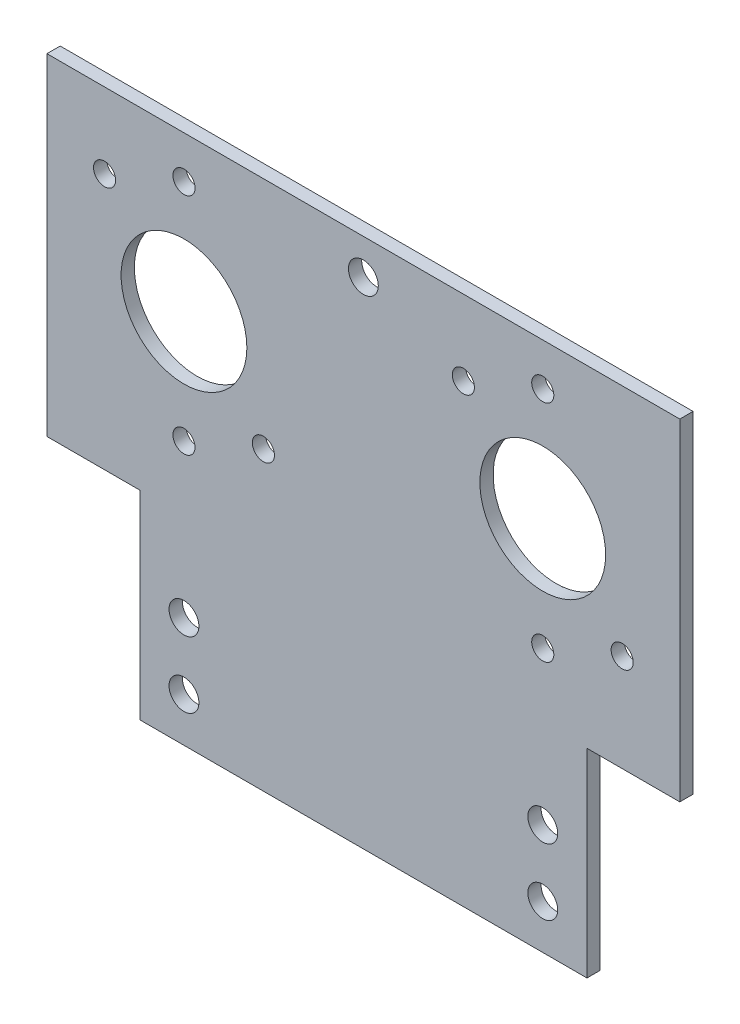
SolidWorks part; units mm, degrees
ref_plane "Front Plane" through (0, 0, 0) normal (0, 0, 1) x (1, 0, 0)
ref_plane "Top Plane" through (0, 0, 0) normal (0, 1, 0) x (1, 0, 0)
ref_plane "Right Plane" through (0, 0, 0) normal (1, 0, 0) x (0, 0, -1)
sketch "Sketch1" plane through (0, 0, 0) normal (0, 0, 1) x (1, 0, 0)
  line L1 (0, 0) -> (143.16, 0)
  line L2 (0, 0) -> (0, -120)
  line L3 (0, -120) -> (143.16, -120)
  line L4 (143.16, 0) -> (143.16, -120)
  dimension "D1" = 120
  dimension "D2" = 143.16
extrude "Boss-Extrude1" add sketch "Sketch1" along normal blind 3
sketch "Sketch2" plane through (0, 0, 3) normal (0, 0, 1) x (1, 0, 0)
  line L0 (0, 0) -> (0, -120) construction
  line L1 (143.16, -120) -> (143.16, 0) construction
  line L2 (0, -120) -> (143.16, -120) construction
  line L3 (143.16, 0) -> (0, 0) construction
  circle A0 centre (31, -35) radius 14.225
  circle A1 centre (112.16, -35) radius 14.225
  circle A2 centre (31, -110) radius 3.375
  circle A5 centre (112.16, -110) radius 3.375
  circle A7 centre (71.58, -8) radius 3.375
  circle A8 centre (31, -95) radius 3.375
  circle A9 centre (112.16, -95) radius 3.375
  point P6 (0, 0)
  point P7 (0, 0)
  point P8 (67.2787, -8)
  point P9 (71.58, 0)
  dimension "D1" = 28.45
  dimension "D2" = 28.45
  dimension "D3" = 6.75
  dimension "D4" = 35
  dimension "D5" = 6.75
  dimension "D7" = 15
  dimension "D8" = 6.75
  dimension "D9" = 31
  dimension "D10" = 31
  dimension "D13" = 15
  dimension "D14" = 10
  dimension "D16" = 8
extrude "Cut-Extrude1" cut sketch "Sketch2" against normal through all
sketch "Sketch3" plane through (0, 0, 0) normal (0, 0, -1) x (-1, 0, 0)
  circle A0 centre (-48.9605, -52.9605) radius 2.0193 construction
  circle A1 centre (-31, -9.6) radius 2.0193 construction
  circle A2 centre (-13.0395, -17.0395) radius 2.0193 construction
  circle A3 centre (-48.9605, -52.9605) radius 2.0193
  circle A4 centre (-31, -9.6) radius 2.0193
  circle A5 centre (-13.0395, -17.0395) radius 2.0193
  circle A6 centre (-31, -60.4) radius 2.0193 construction
  circle A7 centre (-31, -60.4) radius 2.0193
  circle A8 centre (-94.1995, -17.0395) radius 2.0193 construction
  circle A9 centre (-112.16, -9.6) radius 2.0193 construction
  circle A10 centre (-94.1995, -17.0395) radius 2.0193
  circle A11 centre (-112.16, -9.6) radius 2.0193
  circle A12 centre (-112.16, -60.4) radius 2.0193 construction
  circle A13 centre (-130.1205, -52.9605) radius 2.0193 construction
  circle A14 centre (-112.16, -60.4) radius 2.0193
  circle A15 centre (-130.1205, -52.9605) radius 2.0193
  point P25 (-31, -60.4)
  point P26 (-48.9605, -52.9605)
  point P27 (-31, -9.6)
  point P28 (-13.0395, -17.0395)
  point P29 (-112.16, -60.4)
  point P30 (-130.1205, -52.9605)
  point P31 (-112.16, -9.6)
  point P32 (-94.1995, -17.0395)
extrude "Cut-Extrude2" cut sketch "Sketch3" against normal through all
sketch "Sketch6" plane through (0, 0, 3) normal (0, 0, 1) x (1, 0, 0)
  circle A0 centre (31, -60.4) radius 2.5
  circle A1 centre (48.9605, -52.9605) radius 2.5
  circle A3 centre (31, -9.6) radius 2.5
  circle A4 centre (13.0395, -17.0395) radius 2.5
  circle A5 centre (130.1205, -52.9605) radius 2.5
  circle A6 centre (112.16, -60.4) radius 2.5
  circle A7 centre (94.1995, -17.0395) radius 2.5
  circle A8 centre (112.16, -9.6) radius 2.5
  dimension "D1" = 5
  dimension "D2" = 5
  dimension "D3" = 5
  dimension "D4" = 5
  dimension "D5" = 5
  dimension "D6" = 5
  dimension "D7" = 5
  dimension "D8" = 5
extrude "Cut-Extrude3" cut sketch "Sketch6" against normal through all
sketch "Sketch7" plane through (0, 0, 3) normal (0, 0, 1) x (1, 0, 0)
  line L1 (143.16, -120) -> (122.16, -120)
  line L2 (143.16, -120) -> (143.16, -75)
  line L3 (143.16, -75) -> (122.16, -75)
  line L4 (122.16, -120) -> (122.16, -75)
  line L5 (0, -120) -> (21, -120)
  line L6 (0, -120) -> (0, -75)
  line L7 (0, -75) -> (21, -75)
  line L8 (21, -120) -> (21, -75)
  dimension "D1" = 21
  dimension "D2" = 21
  dimension "D3" = 45
  dimension "D4" = 45
extrude "Cut-Extrude4" cut sketch "Sketch7" against normal through all
